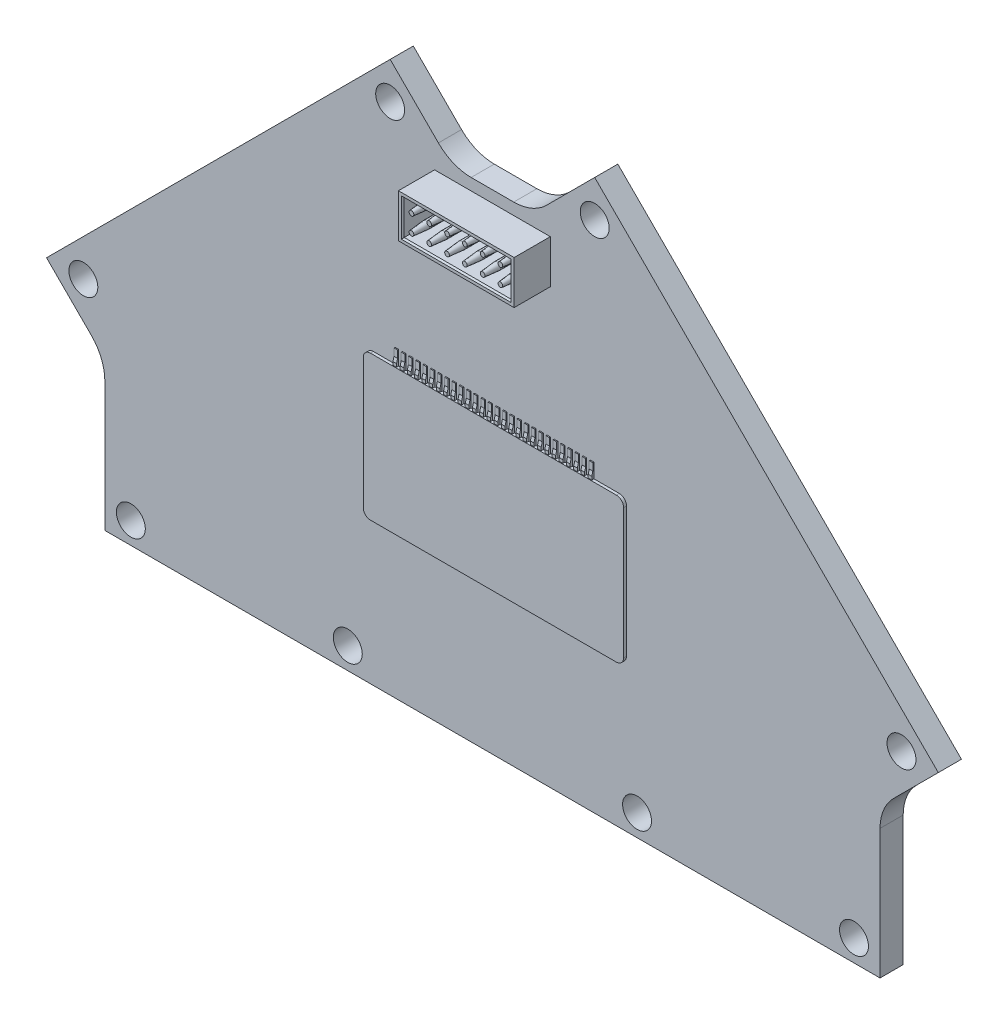
SolidWorks part; units mm, degrees
material "处理板，简单型"
ref_plane "前视基准面" through (0, 0, 0) normal (0, 0, 1) x (1, 0, 0)
ref_plane "上视基准面" through (0, 0, 0) normal (0, 1, 0) x (1, 0, 0)
ref_plane "右视基准面" through (0, 0, 0) normal (1, 0, 0) x (0, 0, -1)
sketch "Model" plane through (0, 0, 0) normal (0, 0, 1) x (1, 0, 0)
  line L7 (13.9194, -7.0717) -> (-2.0806, -7.0717)
  line L8 (-2.0806, -7.0717) -> (-2.0806, -11.9717)
  line L9 (13.9194, -7.0717) -> (13.9194, -11.9717)
  line L10 (-16.0806, -8.9717) -> (27.9194, -8.9717)
  line L11 (-19.0806, 2.9694) -> (-19.0806, -5.9717)
  line L12 (-3.143, 20.1496) -> (-18.2019, 5.0907)
  line L13 (30.9194, 2.9694) -> (30.9194, -5.9717)
  line L14 (14.9819, 20.1496) -> (30.0408, 5.0907)
  line L15 (-1.0217, 21.0283) -> (12.8606, 21.0283)
  line L17 (5.9194, -11.9717) -> (32.7194, -11.9717)
  line L18 (-20.8806, -11.9717) -> (5.9194, -11.9717)
  line L20 (32.7194, -3.0133) -> (32.7194, -11.9717)
  line L21 (36.7493, 2.342) -> (33.6567, -0.7506)
  line L22 (12.9905, 26.1008) -> (36.7493, 2.342)
  line L23 (12.9905, 26.1008) -> (9.6553, 22.7656)
  line L24 (4.4463, 21.8283) -> (7.3925, 21.8283)
  line L25 (-1.1516, 26.1008) -> (2.1836, 22.7656)
  line L26 (-1.1516, 26.1008) -> (-24.9104, 2.342)
  line L27 (-24.9104, 2.342) -> (-21.8178, -0.7506)
  line L28 (-20.8806, -3.0133) -> (-20.8806, -11.9717)
  arc A4 (-19.0806, -5.9717) -> (-16.0806, -8.9717) centre (-16.0806, -5.9717) ccw
  arc A5 (-18.2019, 5.0907) -> (-19.0806, 2.9694) centre (-16.0806, 2.9694) ccw
  arc A6 (27.9194, -8.9717) -> (30.9194, -5.9717) centre (27.9194, -5.9717) ccw
  arc A7 (30.9194, 2.9694) -> (30.0408, 5.0907) centre (27.9194, 2.9694) ccw
  arc A8 (14.9819, 20.1496) -> (12.8606, 21.0283) centre (12.8606, 18.0283) ccw
  arc A9 (-1.0217, 21.0283) -> (-3.143, 20.1496) centre (-1.0217, 18.0283) ccw
  circle A10 centre (12.9905, 23.5552) radius 1
  circle A11 centre (-1.1516, 23.5552) radius 1
  circle A12 centre (-22.3648, 2.342) radius 1
  circle A13 centre (-19.0806, -10.4717) radius 1
  circle A14 centre (-4.0806, -10.4717) radius 1
  circle A15 centre (15.9194, -10.4717) radius 1
  circle A16 centre (30.9194, -10.4717) radius 1
  circle A17 centre (34.2037, 2.342) radius 1
  arc A18 (33.6567, -0.7506) -> (32.7194, -3.0133) centre (35.9194, -3.0133) ccw
  arc A19 (7.3925, 21.8283) -> (9.6553, 22.7656) centre (7.3925, 25.0283) ccw
  arc A20 (2.1836, 22.7656) -> (4.4463, 21.8283) centre (4.4463, 25.0283) ccw
  arc A21 (-20.8806, -3.0133) -> (-21.8178, -0.7506) centre (-24.0806, -3.0133) ccw
extrude "凸台-拉伸1" add sketch "Model" along normal blind 1.6 contours A21 L28 L18 L8 L10 A4 L11 A5 L12 A9 L15 A8 L14 A7 L13 A6 L9 L17 L20 A18 L21 L22 L23 A19 L24 A20 L25 L26 L27 A17 A16 A15 A14 A13 A12 A11 A10 | L8 L18 L17 L9 L10 | L15 A9 L12 A5 L11 A4 L10 L8 L7 L9 A6 L13 A7 L14 A8 | L8 L10 L9 L7 region at (5.9194, -8.0217, 0) region at (5.9194, 4.1849, 0) region at (20.9194, -9.6964, 0) region at (5.9194, -10.4717, 0)
sketch "草图1" plane through (0, 0, 1.6) normal (0, 0, 1) x (1, 0, 0)
  line L0 (-20.8806, -11.9717) -> (32.7194, -11.9717) construction
  line L1 (-2.3112, 8.0283) -> (14.6888, 8.0283)
  line L2 (-2.8112, 7.5283) -> (-2.8112, -1.4717)
  line L3 (-2.3112, -1.9717) -> (14.6888, -1.9717)
  line L4 (15.1888, 7.5283) -> (15.1888, -1.4717)
  line L5 (-2.8112, 8.0283) -> (15.1888, -1.9717) construction
  line L6 (-2.8112, -1.9717) -> (15.1888, 8.0283) construction
  arc A0 (14.6888, 8.0283) -> (15.1888, 7.5283) centre (14.6888, 7.5283) cw
  arc A1 (15.1888, -1.4717) -> (14.6888, -1.9717) centre (14.6888, -1.4717) cw
  arc A2 (-2.3112, -1.9717) -> (-2.8112, -1.4717) centre (-2.3112, -1.4717) cw
  arc A3 (-2.8112, 7.5283) -> (-2.3112, 8.0283) centre (-2.3112, 7.5283) cw
  point P0 (6.1888, 3.0283)
  dimension "D4" = 0.5
  dimension "D1" = 18
  dimension "D2" = 10
  dimension "D3" = 10
extrude "凸台-拉伸2" add sketch "草图1" along normal blind 0.2
sketch "草图2" plane through (0, 0, 1.6) normal (0, 0, 1) x (1, 0, 0)
  line L1 (1.9194, 21.0201) -> (9.9194, 21.0201)
  line L2 (1.9194, 21.0201) -> (1.9194, 18.0201)
  line L3 (1.9194, 18.0201) -> (9.9194, 18.0201)
  line L4 (9.9194, 21.0201) -> (9.9194, 18.0201)
  line L7 (4.4463, 21.8283) -> (7.3925, 21.8283) construction
  line L8 (2.2194, 20.7201) -> (9.6194, 20.7201)
  line L9 (9.6194, 20.7201) -> (9.6194, 18.3201)
  line L10 (2.2194, 18.3201) -> (9.6194, 18.3201)
  line L11 (2.2194, 20.7201) -> (2.2194, 18.3201)
  circle A0 centre (2.8194, 20.1201) radius 0.25
  circle A1 centre (2.8194, 18.9201) radius 0.25
  circle A2 centre (4.0494, 20.1201) radius 0.25
  circle A3 centre (4.0494, 18.9201) radius 0.25
  circle A4 centre (5.2794, 20.1201) radius 0.25
  circle A5 centre (5.2794, 18.9201) radius 0.25
  circle A6 centre (6.5094, 20.1201) radius 0.25
  circle A7 centre (6.5094, 18.9201) radius 0.25
  circle A8 centre (7.7394, 20.1201) radius 0.25
  circle A9 centre (7.7394, 18.9201) radius 0.25
  circle A10 centre (8.9694, 20.1201) radius 0.25
  circle A11 centre (8.9694, 18.9201) radius 0.25
  dimension "D3" = 0.5
  dimension "D5" = 0.5
  dimension "D6" = 0.6
  dimension "D7" = 0.6
  dimension "D8" = 0.6
  dimension "D9" = 0.6
  dimension "D1" = 8
  dimension "D2" = 3
  dimension "D4" = 0.3
  dimension "D10" = 6
extrude "凸台-拉伸3" add sketch "草图2" along normal blind 2.5 contours L4 L1 L2 L3 L11 L8 L9 L10 | A1 | A0 | A2 | A3 | A4 | A5 | A6 | A7 | A8 | A9 | A11 | A10 region at (5.9194, 20.9347, 1.6) region at (2.8194, 20.1201, 1.6) region at (2.8194, 18.9201, 1.6) region at (4.0494, 20.1201, 1.6) region at (4.0494, 18.9201, 1.6) region at (5.2794, 20.1201, 1.6) region at (5.2794, 18.9201, 1.6) region at (6.5094, 20.1201, 1.6) region at (6.5094, 18.9201, 1.6) region at (7.7394, 20.1201, 1.6) region at (7.7394, 18.9201, 1.6) region at (8.9694, 20.1201, 1.6) region at (8.9694, 18.9201, 1.6)
chamfer "倒角1" distance 1 angle 5 1 edges at (9.2194, 18.9201, 4.1) first distance on face at (9.2194, 18.9201, 4.1)
chamfer "倒角2" distance 1 angle 5 11 edges at (4.2994, 20.1201, 4.1) (3.0694, 20.1201, 4.1) (3.0694, 18.9201, 4.1) (4.2994, 18.9201, 4.1) (5.5294, 20.1201, 4.1) (5.5294, 18.9201, 4.1) (6.7594, 20.1201, 4.1) (6.7594, 18.9201, 4.1) (7.9894, 20.1201, 4.1) (7.9894, 18.9201, 4.1) (9.2194, 20.1201, 4.1) first distance on face at (4.2994, 20.1201, 4.1) first distance on face at (3.0694, 20.1201, 4.1) first distance on face at (3.0694, 18.9201, 4.1) first distance on face at (4.2994, 18.9201, 4.1) first distance on face at (5.5294, 20.1201, 4.1) first distance on face at (5.5294, 18.9201, 4.1) first distance on face at (6.7594, 20.1201, 4.1) first distance on face at (6.7594, 18.9201, 4.1) first distance on face at (7.9894, 20.1201, 4.1) first distance on face at (7.9894, 18.9201, 4.1) first distance on face at (9.2194, 20.1201, 4.1)
chamfer "倒角3" distance 0.1 angle 45 4 edges at (9.6194, 19.5201, 4.1) (5.9194, 20.7201, 4.1) (2.2194, 19.5201, 4.1) (5.9194, 18.3201, 4.1)
sketch "草图4" plane through (0, 0, 0) normal (0, 0, -1) x (-1, 0, 0)
  line L0 (20.8806, -11.9717) -> (-32.7194, -11.9717) construction
  line L1 (-10.9194, -11.9717) -> (-0.9194, -11.9717)
  line L2 (-10.9194, -11.9717) -> (-10.9194, -8.9717)
  line L3 (-10.9194, -8.9717) -> (-0.9194, -8.9717)
  line L4 (-0.9194, -11.9717) -> (-0.9194, -8.9717)
  circle A0 centre (-15.9194, -10.4717) radius 1 construction
  dimension "D3" = 5
  dimension "D1" = 10
  dimension "D2" = 3
extrude "凸台-拉伸5" add sketch "草图4" along normal blind 2
sketch "草图6" plane through (0, 0, -2) normal (0, 0, -1) x (-1, 0, 0)
  line L0 (-10.9194, -11.9717) -> (-0.9194, -11.9717) construction
  line L1 (-9.9194, -11.4717) -> (-1.9194, -11.4717)
  line L2 (-9.9194, -11.4717) -> (-9.9194, -11.9717)
  line L3 (-9.9194, -11.9717) -> (-1.9194, -11.9717)
  line L4 (-1.9194, -11.4717) -> (-1.9194, -11.9717)
  line L5 (-0.9194, -11.9717) -> (-0.9194, -8.9717) construction
  dimension "D1" = 8
  dimension "D2" = 1
  dimension "D3" = 0.5
extrude "切除-拉伸1" cut sketch "草图6" against normal blind 1
sketch "草图7" plane through (0, -11.9717, 0) normal (0, -1, 0) x (1, 0, 0)
  line L0 (-20.8806, 0) -> (0.9194, 0) construction
  line L1 (1.2194, 0) -> (10.6194, 0)
  line L2 (1.2194, 0) -> (1.2194, -1.7)
  line L3 (1.2194, -1.7) -> (10.6194, -1.7)
  line L4 (10.6194, 0) -> (10.6194, -1.7)
  line L5 (0.9194, -2) -> (0.9194, 0) construction
  line L6 (10.9194, -2) -> (10.9194, 0) construction
  point P6 (0.9194, -1)
  dimension "D1" = 1.7
  dimension "D2" = 0
  dimension "D3" = 0.3
  dimension "D4" = 0.3
extrude "切除-拉伸2" cut sketch "草图7" against normal blind 2.7
sketch "草图11" plane through (0, -9.2717, 0) normal (0, -1, 0) x (1, 0, 0)
  line L0 (1.2194, 0) -> (1.2194, -1.7) construction
  circle A0 centre (2.1694, -0.85) radius 0.25
  circle A1 centre (3.6694, -0.85) radius 0.25
  circle A2 centre (5.1694, -0.85) radius 0.25
  circle A3 centre (6.6694, -0.85) radius 0.25
  circle A4 centre (8.1694, -0.85) radius 0.25
  circle A5 centre (9.6694, -0.85) radius 0.25
  point P2 (1.2194, -0.85)
  dimension "D1" = 0.5
  dimension "D2" = 0.95
  dimension "D3" = 6
extrude "凸台-拉伸9" add sketch "草图11" along normal blind 2.5
chamfer "倒角6" distance 1 angle 5 6 edges at (6.6694, -11.7717, -1.1) (3.6694, -11.7717, -1.1) (9.6694, -11.7717, -1.1) (8.1694, -11.7717, -1.1) (5.1694, -11.7717, -1.1) (2.1694, -11.7717, -1.1) first distance on face at (6.6694, -11.7717, -1.1) first distance on face at (3.6694, -11.7717, -1.1) first distance on face at (9.6694, -11.7717, -1.1) first distance on face at (8.1694, -11.7717, -1.1) first distance on face at (5.1694, -11.7717, -1.1) first distance on face at (2.1694, -11.7717, -1.1)
sketch "草图12" plane through (0, 0, 0) normal (0, 0, -1) x (-1, 0, 0)
  line L0 (-0.9194, -8.9717) -> (-10.9194, -8.9717) construction
  line L1 (-9.9694, -7.9717) -> (-9.6694, -7.9717)
  line L2 (-9.9694, -7.9717) -> (-9.9694, -8.9717)
  line L3 (-9.9694, -8.9717) -> (-9.6694, -8.9717)
  line L4 (-9.6694, -7.9717) -> (-9.6694, -8.9717)
  line L5 (-10.9194, -8.9717) -> (-10.9194, -11.9717) construction
  line L6 (-8.4694, -7.9717) -> (-8.1694, -7.9717)
  line L7 (-8.4694, -7.9717) -> (-8.4694, -8.9717)
  line L8 (-8.1694, -7.9717) -> (-8.1694, -8.9717)
  line L9 (-8.4694, -8.9717) -> (-8.1694, -8.9717)
  line L10 (-6.9694, -7.9717) -> (-6.6694, -7.9717)
  line L11 (-6.9694, -7.9717) -> (-6.9694, -8.9717)
  line L12 (-6.6694, -7.9717) -> (-6.6694, -8.9717)
  line L13 (-6.9694, -8.9717) -> (-6.6694, -8.9717)
  line L14 (-5.4694, -7.9717) -> (-5.1694, -7.9717)
  line L15 (-5.4694, -7.9717) -> (-5.4694, -8.9717)
  line L16 (-5.1694, -7.9717) -> (-5.1694, -8.9717)
  line L17 (-5.4694, -8.9717) -> (-5.1694, -8.9717)
  line L18 (-3.9694, -7.9717) -> (-3.6694, -7.9717)
  line L19 (-3.9694, -7.9717) -> (-3.9694, -8.9717)
  line L20 (-3.6694, -7.9717) -> (-3.6694, -8.9717)
  line L21 (-3.9694, -8.9717) -> (-3.6694, -8.9717)
  line L22 (-2.4694, -7.9717) -> (-2.1694, -7.9717)
  line L23 (-2.4694, -7.9717) -> (-2.4694, -8.9717)
  line L24 (-2.1694, -7.9717) -> (-2.1694, -8.9717)
  line L25 (-2.4694, -8.9717) -> (-2.1694, -8.9717)
  dimension "D1" = 0.3
  dimension "D2" = 1
  dimension "D3" = 0.95
  dimension "D4" = 6
extrude "凸台-拉伸10" add sketch "草图12" along normal blind 1.5
sketch "草图13" plane through (9.9694, 0, 0) normal (1, 0, 0) x (0, 0, -1)
  line L0 (0.75, -7.9717) -> (1.5, -8.4717)
  line L1 (1.5, -7.9717) -> (0, -7.9717) construction
  line L2 (1.5, -7.9717) -> (1.5, -8.9717) construction
  line L3 (1.5, -8.4717) -> (1.5, -7.9717)
  line L4 (1.5, -7.9717) -> (0.75, -7.9717)
extrude "切除-拉伸4" cut sketch "草图13" against normal blind 8.5
sketch "草图14" plane through (9.9694, 0, 0) normal (1, 0, 0) x (0, 0, -1)
  line L0 (0, -8.6717) -> (0, -8.9717)
  line L1 (0, -7.9717) -> (0, -8.9717) construction
  line L2 (0, -8.9717) -> (0.5615, -8.9717)
  line L3 (1.5, -8.9717) -> (0, -8.9717) construction
  line L4 (0.5615, -8.9717) -> (0.2, -8.6717)
  line L5 (0.2, -8.6717) -> (0, -8.6717)
  line L6 (0.75, -7.9717) -> (1.5, -8.4717) construction
  dimension "D1" = 0.3
  dimension "D2" = 0.2
  dimension "D3" = 6
extrude "切除-拉伸5" cut sketch "草图14" against normal blind 8.5
sketch "草图15" plane through (0, 0, 0) normal (0, 0, -1) x (-1, 0, 0)
  line L0 (20.8806, -11.9717) -> (-0.9194, -11.9717) construction
  line L1 (-11.9194, 10.0283) -> (0.0806, 10.0283)
  line L2 (-11.9194, 10.0283) -> (-11.9194, -1.9717)
  line L3 (-11.9194, -1.9717) -> (0.0806, -1.9717)
  line L4 (0.0806, 10.0283) -> (0.0806, -1.9717)
  line L5 (-11.9194, 10.0283) -> (0.0806, -1.9717) construction
  line L6 (-11.9194, -1.9717) -> (0.0806, 10.0283) construction
  point P0 (-5.9194, 4.0283)
  dimension "D1" = 16
  dimension "D2" = 12
  dimension "D3" = 12
extrude "凸台-拉伸11" add sketch "草图15" along normal blind 1.2
chamfer "倒角7" distance 0.2 angle 45 4 edges at (5.9194, -1.9717, -1.2) (-0.0806, 4.0283, -1.2) (11.9194, 4.0283, -1.2) (5.9194, 10.0283, -1.2)
chamfer "倒角8" distance 0.2 angle 45 4 edges at (11.9194, -1.9717, -0.5) (-0.0806, -1.9717, -0.5) (-0.0806, 10.0283, -0.5) (11.9194, 10.0283, -0.5)
sketch "草图16" plane through (0, 0, 0) normal (0, 0, -1) x (-1, 0, 0)
  line L0 (-11.9194, 9.8283) -> (-11.9194, -1.7717) construction
  line L1 (-21.9194, 11.0283) -> (-16.9194, 11.0283)
  line L2 (-21.9194, 11.0283) -> (-21.9194, 6.0283)
  line L3 (-21.9194, 6.0283) -> (-16.9194, 6.0283)
  line L4 (-16.9194, 11.0283) -> (-16.9194, 6.0283)
  line L5 (-21.9194, 11.0283) -> (-16.9194, 6.0283) construction
  line L6 (-21.9194, 6.0283) -> (-16.9194, 11.0283) construction
  line L7 (-10.9194, -11.9717) -> (-32.7194, -11.9717) construction
  point P0 (-19.4194, 8.5283)
  dimension "D1" = 5
  dimension "D2" = 5
  dimension "D3" = 5
  dimension "D4" = 18
extrude "凸台-拉伸12" add sketch "草图16" along normal blind 1.2
sketch "草图17" plane through (0, 0, 0) normal (0, 0, -1) x (-1, 0, 0)
  line L0 (0.0806, -1.7717) -> (0.0806, 9.8283) construction
  line L1 (4.0806, 5.5424) -> (7.0806, 5.5424)
  line L2 (4.0806, 5.5424) -> (4.0806, 0.5424)
  line L3 (4.0806, 0.5424) -> (7.0806, 0.5424)
  line L4 (7.0806, 5.5424) -> (7.0806, 0.5424)
  line L5 (11.0806, 3.0283) -> (16.0806, 3.0283)
  line L6 (11.0806, 3.0283) -> (11.0806, 0.0283)
  line L7 (11.0806, 0.0283) -> (16.0806, 0.0283)
  line L8 (16.0806, 3.0283) -> (16.0806, 0.0283)
  line L9 (20.8806, -11.9717) -> (-0.9194, -11.9717) construction
  line L11 (-21.5783, 0.2667) -> (-19.5783, 0.2667)
  line L12 (-21.5783, 0.2667) -> (-21.5783, -2.7333)
  line L13 (-21.5783, -2.7333) -> (-19.5783, -2.7333)
  line L14 (-19.5783, 0.2667) -> (-19.5783, -2.7333)
  dimension "D1" = 3
  dimension "D2" = 5
  dimension "D3" = 4
  dimension "D4" = 5
  dimension "D5" = 3
  dimension "D6" = 12
  dimension "D7" = 4
  dimension "D8" = 3
  dimension "D9" = 2
extrude "凸台-拉伸13" add sketch "草图17" along normal blind 1.2
chamfer "倒角9" distance 0.2 angle 45 16 edges at (-13.5806, 3.0283, -1.2) (-16.0806, 1.5283, -1.2) (-13.5806, 0.0283, -1.2) (-11.0806, 1.5283, -1.2) (-5.5806, 5.5424, -1.2) (-7.0806, 3.0424, -1.2) (-5.5806, 0.5424, -1.2) (-4.0806, 3.0424, -1.2) (20.5783, 0.2667, -1.2) (19.5783, -1.2333, -1.2) (20.5783, -2.7333, -1.2) (21.5783, -1.2333, -1.2) (19.4194, 6.0283, -1.2) (21.9194, 8.5283, -1.2) (19.4194, 11.0283, -1.2) (16.9194, 8.5283, -1.2)
chamfer "倒角10" distance 0.2 angle 45 16 edges at (-16.0806, 0.0283, -0.5) (-16.0806, 3.0283, -0.5) (-11.0806, 3.0283, -0.5) (-11.0806, 0.0283, -0.5) (-7.0806, 0.5424, -0.5) (-7.0806, 5.5424, -0.5) (-4.0806, 5.5424, -0.5) (-4.0806, 0.5424, -0.5) (19.5783, 0.2667, -0.5) (21.5783, 0.2667, -0.5) (19.5783, -2.7333, -0.5) (21.5783, -2.7333, -0.5) (21.9194, 6.0283, -0.5) (16.9194, 6.0283, -0.5) (16.9194, 11.0283, -0.5) (21.9194, 11.0283, -0.5)
sketch "草图18" plane through (0, 0, 0) normal (0, 0, -1) x (-1, 0, 0)
  line L0 (-16.9194, 6.2283) -> (-16.9194, 10.8283) construction
  line L1 (-16.9194, 10.5283) -> (-15.7194, 10.5283)
  line L2 (-16.9194, 10.5283) -> (-16.9194, 10.2283)
  line L3 (-16.9194, 10.2283) -> (-15.7194, 10.2283)
  line L4 (-15.7194, 10.5283) -> (-15.7194, 10.2283)
  line L5 (-21.7194, 11.0283) -> (-17.1194, 11.0283) construction
  line L6 (-16.9194, 9.9283) -> (-15.7194, 9.9283)
  line L7 (-16.9194, 9.6283) -> (-15.7194, 9.6283)
  line L8 (-15.7194, 9.9283) -> (-15.7194, 9.6283)
  line L9 (-16.9194, 9.9283) -> (-16.9194, 9.6283)
  line L10 (-16.9194, 9.3283) -> (-15.7194, 9.3283)
  line L11 (-16.9194, 9.0283) -> (-15.7194, 9.0283)
  line L12 (-15.7194, 9.3283) -> (-15.7194, 9.0283)
  line L13 (-16.9194, 9.3283) -> (-16.9194, 9.0283)
  line L14 (-16.9194, 8.7283) -> (-15.7194, 8.7283)
  line L15 (-16.9194, 8.4283) -> (-15.7194, 8.4283)
  line L16 (-15.7194, 8.7283) -> (-15.7194, 8.4283)
  line L17 (-16.9194, 8.7283) -> (-16.9194, 8.4283)
  line L18 (-16.9194, 8.1283) -> (-15.7194, 8.1283)
  line L19 (-16.9194, 7.8283) -> (-15.7194, 7.8283)
  line L20 (-15.7194, 8.1283) -> (-15.7194, 7.8283)
  line L21 (-16.9194, 8.1283) -> (-16.9194, 7.8283)
  line L22 (-16.9194, 7.5283) -> (-15.7194, 7.5283)
  line L23 (-16.9194, 7.2283) -> (-15.7194, 7.2283)
  line L24 (-15.7194, 7.5283) -> (-15.7194, 7.2283)
  line L25 (-16.9194, 7.5283) -> (-16.9194, 7.2283)
  line L26 (-16.9194, 6.9283) -> (-15.7194, 6.9283)
  line L27 (-16.9194, 6.6283) -> (-15.7194, 6.6283)
  line L28 (-15.7194, 6.9283) -> (-15.7194, 6.6283)
  line L29 (-16.9194, 6.9283) -> (-16.9194, 6.6283)
  line L31 (-21.9194, 10.8283) -> (-21.9194, 6.2283) construction
  line L32 (-21.4194, 12.2283) -> (-21.1194, 12.2283)
  line L33 (-21.4194, 12.2283) -> (-21.4194, 11.0283)
  line L34 (-21.4194, 11.0283) -> (-21.1194, 11.0283)
  line L35 (-21.1194, 12.2283) -> (-21.1194, 11.0283)
  line L36 (-20.5194, 12.2283) -> (-20.5194, 11.0283)
  line L37 (-20.8194, 12.2283) -> (-20.8194, 11.0283)
  line L38 (-20.8194, 12.2283) -> (-20.5194, 12.2283)
  line L39 (-20.8194, 11.0283) -> (-20.5194, 11.0283)
  line L40 (-19.9194, 12.2283) -> (-19.9194, 11.0283)
  line L41 (-20.2194, 12.2283) -> (-20.2194, 11.0283)
  line L42 (-20.2194, 12.2283) -> (-19.9194, 12.2283)
  line L43 (-20.2194, 11.0283) -> (-19.9194, 11.0283)
  line L44 (-19.3194, 12.2283) -> (-19.3194, 11.0283)
  line L45 (-19.6194, 12.2283) -> (-19.6194, 11.0283)
  line L46 (-19.6194, 12.2283) -> (-19.3194, 12.2283)
  line L47 (-19.6194, 11.0283) -> (-19.3194, 11.0283)
  line L48 (-18.7194, 12.2283) -> (-18.7194, 11.0283)
  line L49 (-19.0194, 12.2283) -> (-19.0194, 11.0283)
  line L50 (-19.0194, 12.2283) -> (-18.7194, 12.2283)
  line L51 (-19.0194, 11.0283) -> (-18.7194, 11.0283)
  line L52 (-18.1194, 12.2283) -> (-18.1194, 11.0283)
  line L53 (-18.4194, 12.2283) -> (-18.4194, 11.0283)
  line L54 (-18.4194, 12.2283) -> (-18.1194, 12.2283)
  line L55 (-18.4194, 11.0283) -> (-18.1194, 11.0283)
  line L56 (-17.5194, 12.2283) -> (-17.5194, 11.0283)
  line L57 (-17.8194, 12.2283) -> (-17.8194, 11.0283)
  line L58 (-17.8194, 12.2283) -> (-17.5194, 12.2283)
  line L59 (-17.8194, 11.0283) -> (-17.5194, 11.0283)
  line L60 (-17.1194, 6.0283) -> (-21.7194, 6.0283) construction
  line L61 (-23.1194, 6.8283) -> (-21.9194, 6.8283)
  line L62 (-23.1194, 6.8283) -> (-23.1194, 6.5283)
  line L63 (-23.1194, 6.5283) -> (-21.9194, 6.5283)
  line L64 (-21.9194, 6.8283) -> (-21.9194, 6.5283)
  line L65 (-23.1194, 7.4283) -> (-21.9194, 7.4283)
  line L66 (-23.1194, 7.4283) -> (-23.1194, 7.1283)
  line L67 (-23.1194, 7.1283) -> (-21.9194, 7.1283)
  line L68 (-21.9194, 7.4283) -> (-21.9194, 7.1283)
  line L69 (-23.1194, 8.0283) -> (-21.9194, 8.0283)
  line L70 (-23.1194, 8.0283) -> (-23.1194, 7.7283)
  line L71 (-23.1194, 7.7283) -> (-21.9194, 7.7283)
  line L72 (-21.9194, 8.0283) -> (-21.9194, 7.7283)
  line L73 (-23.1194, 8.6283) -> (-21.9194, 8.6283)
  line L74 (-23.1194, 8.6283) -> (-23.1194, 8.3283)
  line L75 (-23.1194, 8.3283) -> (-21.9194, 8.3283)
  line L76 (-21.9194, 8.6283) -> (-21.9194, 8.3283)
  line L77 (-23.1194, 9.2283) -> (-21.9194, 9.2283)
  line L78 (-23.1194, 9.2283) -> (-23.1194, 8.9283)
  line L79 (-23.1194, 8.9283) -> (-21.9194, 8.9283)
  line L80 (-21.9194, 9.2283) -> (-21.9194, 8.9283)
  line L81 (-23.1194, 9.8283) -> (-21.9194, 9.8283)
  line L82 (-23.1194, 9.8283) -> (-23.1194, 9.5283)
  line L83 (-23.1194, 9.5283) -> (-21.9194, 9.5283)
  line L84 (-21.9194, 9.8283) -> (-21.9194, 9.5283)
  line L85 (-23.1194, 10.4283) -> (-21.9194, 10.4283)
  line L86 (-23.1194, 10.4283) -> (-23.1194, 10.1283)
  line L87 (-23.1194, 10.1283) -> (-21.9194, 10.1283)
  line L88 (-21.9194, 10.4283) -> (-21.9194, 10.1283)
  dimension "D1" = 1.2
  dimension "D2" = 0.3
  dimension "D3" = 0.5
  dimension "D5" = 1.2
  dimension "D6" = 0.3
  dimension "D7" = 0.5
  dimension "D9" = 1.2
  dimension "D10" = 0.3
  dimension "D11" = 0.5
  dimension "D4" = 7
  dimension "D8" = 7
  dimension "D12" = 7
extrude "凸台-拉伸14" add sketch "草图18" along normal blind 0.6
sketch "草图19" plane through (0, 6.6283, 0) normal (0, -1, 0) x (1, 0, 0)
  line L0 (15.7194, -0.2) -> (16.0992, -0.2)
  line L1 (15.7194, -0.6) -> (15.7194, 0) construction
  line L2 (16.0992, -0.2) -> (16.5759, -0.6)
  line L3 (16.9194, -0.6) -> (15.7194, -0.6) construction
  line L4 (16.5759, -0.6) -> (15.7194, -0.6)
  line L5 (15.7194, -0.6) -> (15.7194, -0.2)
  line L6 (16.9194, 0) -> (15.7194, 0) construction
  line L7 (16.473, 0) -> (16.9194, -0.3908)
  line L8 (10.9194, 0) -> (32.7194, 0) construction
  line L9 (16.9194, -0.6) -> (16.9194, 0) construction
  line L10 (16.9194, -0.3908) -> (16.9194, 0)
  line L11 (16.9194, 0) -> (16.473, 0)
  dimension "D1" = 0.2
  dimension "D2" = 40
  dimension "D3" = 1.2
extrude "切除-拉伸6" cut sketch "草图19" against normal blind 4.6
sketch "草图20" plane through (21.4194, 0, 0) normal (1, 0, 0) x (0, 0, -1)
  line L0 (0.2, 12.2283) -> (0.2, 11.8486)
  line L1 (0.6, 12.2283) -> (0, 12.2283) construction
  line L2 (0.2, 11.8486) -> (0.6, 11.3719)
  line L3 (0.6, 12.2283) -> (0.6, 11.0283) construction
  line L4 (0.6, 11.3719) -> (0.6, 12.2283)
  line L5 (0.6, 12.2283) -> (0.2, 12.2283)
  line L6 (0, 12.2283) -> (0, 11.0283) construction
  line L7 (0, 11.0283) -> (0, 11.4122)
  line L8 (0, 11.4122) -> (0.3361, 11.0283)
  line L9 (0.6, 11.0283) -> (0, 11.0283) construction
  line L10 (0.3361, 11.0283) -> (0, 11.0283)
  dimension "D1" = 0.2
  dimension "D2" = 40
  dimension "D3" = 1.2
extrude "切除-拉伸7" cut sketch "草图20" against normal blind 4.6
sketch "草图21" plane through (0, 10.4283, 0) normal (0, 1, 0) x (1, 0, 0)
  line L0 (23.1194, 0.2) -> (22.6256, 0.2)
  line L2 (23.1194, 0.6) -> (23.1194, 0) construction
  line L3 (22.6256, 0.2) -> (22.1489, 0.6)
  line L4 (21.9194, 0.6) -> (23.1194, 0.6) construction
  line L5 (22.1489, 0.6) -> (23.1194, 0.6)
  line L6 (23.1194, 0.6) -> (23.1194, 0.2)
  line L7 (21.9194, 0) -> (22.3441, 0)
  line L8 (12.9905, 0) -> (36.7493, 0) construction
  line L9 (22.3441, 0) -> (21.9194, 0.3717)
  line L10 (21.9194, 0.6) -> (21.9194, 0) construction
  line L11 (21.9194, 0.3717) -> (21.9194, 0)
  line L12 (21.9194, 0) -> (23.1194, 0) construction
  dimension "D1" = 0.2
  dimension "D2" = 40
  dimension "D3" = 1.2
extrude "切除-拉伸8" cut sketch "草图21" against normal blind 4.6
sketch "草图22" plane through (0, 0, 0) normal (0, 0, -1) x (-1, 0, 0)
  line L0 (-21.5783, 0.0667) -> (-21.5783, -2.5333) construction
  line L1 (-22.7783, -0.3333) -> (-21.5783, -0.3333)
  line L2 (-22.7783, -0.3333) -> (-22.7783, -0.6333)
  line L3 (-22.7783, -0.6333) -> (-21.5783, -0.6333)
  line L4 (-21.5783, -0.3333) -> (-21.5783, -0.6333)
  line L5 (-19.5783, -2.5333) -> (-19.5783, 0.0667) construction
  line L6 (-22.7783, -1.8333) -> (-21.5783, -1.8333)
  line L7 (-22.7783, -1.8333) -> (-22.7783, -2.1333)
  line L8 (-22.7783, -2.1333) -> (-21.5783, -2.1333)
  line L9 (-21.5783, -1.8333) -> (-21.5783, -2.1333)
  line L10 (-19.5783, -0.1333) -> (-18.3783, -0.1333)
  line L11 (-19.5783, -0.1333) -> (-19.5783, -0.4333)
  line L12 (-19.5783, -0.4333) -> (-18.3783, -0.4333)
  line L13 (-18.3783, -0.1333) -> (-18.3783, -0.4333)
  line L14 (-21.3783, 0.2667) -> (-19.7783, 0.2667) construction
  line L15 (-19.5783, -1.2333) -> (-18.3783, -1.2333)
  line L16 (-19.5783, -1.2333) -> (-19.5783, -1.5333)
  line L17 (-19.5783, -1.5333) -> (-18.3783, -1.5333)
  line L18 (-18.3783, -1.2333) -> (-18.3783, -1.5333)
  line L19 (-19.5783, -2.0333) -> (-18.3783, -2.0333)
  line L20 (-19.5783, -2.0333) -> (-19.5783, -2.3333)
  line L21 (-19.5783, -2.3333) -> (-18.3783, -2.3333)
  line L22 (-18.3783, -2.0333) -> (-18.3783, -2.3333)
  line L23 (-19.7783, -2.7333) -> (-21.3783, -2.7333) construction
  line L24 (-19.7783, 0.2667) -> (-21.3783, 0.2667) construction
  dimension "D1" = 0.3
  dimension "D2" = 1.2
  dimension "D3" = 1.2
  dimension "D4" = 0.3
  dimension "D5" = 0.3
  dimension "D6" = 0.3
  dimension "D7" = 0.3
  dimension "D8" = 1.2
  dimension "D9" = 1.2
  dimension "D10" = 1.2
  dimension "D11" = 0.6
  dimension "D12" = 0.6
  dimension "D13" = 0.4
  dimension "D14" = 0.4
  dimension "D15" = 1.2
extrude "凸台-拉伸15" add sketch "草图22" along normal blind 0.8
sketch "草图23" plane through (0, -2.3333, 0) normal (0, -1, 0) x (1, 0, 0)
  line L0 (18.3783, -0.2) -> (18.4633, -0.2)
  line L1 (18.3783, -0.8) -> (18.3783, 0) construction
  line L2 (18.4633, -0.2) -> (19.1783, -0.8)
  line L3 (19.5783, -0.8) -> (18.3783, -0.8) construction
  line L4 (19.1783, -0.8) -> (18.3783, -0.8)
  line L5 (18.3783, -0.8) -> (18.3783, -0.2)
  line L6 (19.5783, 0) -> (19.5783, -0.5035)
  line L7 (19.5783, -0.8) -> (19.5783, 0) construction
  line L8 (19.5783, -0.5035) -> (18.9783, 0)
  line L9 (19.5783, 0) -> (18.3783, 0) construction
  line L10 (18.9783, 0) -> (19.5783, 0)
  line L11 (19.5783, 0) -> (19.5938, -0.0006)
  line L12 (10.9194, 0) -> (32.7194, 0) construction
  line L13 (22.7783, -0.2) -> (22.6934, -0.2)
  line L14 (22.7783, -0.8) -> (22.7783, 0) construction
  line L15 (22.6934, -0.2) -> (21.9783, -0.8)
  line L16 (22.7783, -0.8) -> (21.5783, -0.8) construction
  line L17 (21.9783, -0.8) -> (22.7783, -0.8)
  line L18 (22.7783, -0.8) -> (22.7783, -0.2)
  line L19 (21.5783, 0) -> (21.5783, -0.5035)
  line L20 (21.5783, 0) -> (21.5783, -1) construction
  line L21 (21.5783, -0.5035) -> (22.1783, 0)
  line L22 (22.1783, 0) -> (21.5783, 0)
  line L23 (21.5783, 0) -> (21.5597, -0.0047)
  line M1 (19.5783, 0) -> (18.3783, 0)
  line M2 (18.3783, 0) -> (18.3783, -0.8)
  line M3 (18.3783, -0.8) -> (19.5783, -0.8)
  line M4 (19.5783, -0.8) -> (19.5783, 0)
  dimension "D1" = 0.2
  dimension "D2" = 40
  dimension "D3" = 0.8
  dimension "D4" = 360
  dimension "D5" = 0.6
  dimension "D6" = 0.2
  dimension "D7" = 0.8
  dimension "D8" = 40
  dimension "D9" = 50
  dimension "D10" = 0.6
extrude "切除-拉伸9" cut sketch "草图23" against normal blind 3.8 contours L2 L0 M2 M3 | L8 M4 M1 | L21 L22 L19 | L17 L18 L13 L15 region at (18.6477, -2.3333, -0.5808) region at (19.3783, -2.3333, -0.1678) region at (22.5089, -2.3333, -0.5808) region at (21.7783, -2.3333, -0.1678)
sketch "草图24" plane through (0, 0, 0) normal (0, 0, -1) x (-1, 0, 0)
  line L0 (11.2806, 0.0283) -> (15.8806, 0.0283) construction
  line L1 (11.6806, 0.0283) -> (11.9806, 0.0283)
  line L2 (11.6806, 0.0283) -> (11.6806, -1.1717)
  line L3 (11.6806, -1.1717) -> (11.9806, -1.1717)
  line L4 (11.9806, 0.0283) -> (11.9806, -1.1717)
  line L6 (11.0806, 2.8283) -> (11.0806, 0.2283) construction
  line L7 (12.8306, 0.0283) -> (12.8306, -1.1717)
  line L8 (13.1306, 0.0283) -> (13.1306, -1.1717)
  line L9 (12.8306, 0.0283) -> (13.1306, 0.0283)
  line L10 (12.8306, -1.1717) -> (13.1306, -1.1717)
  line L11 (13.9806, 0.0283) -> (13.9806, -1.1717)
  line L12 (14.2806, 0.0283) -> (14.2806, -1.1717)
  line L13 (13.9806, 0.0283) -> (14.2806, 0.0283)
  line L14 (13.9806, -1.1717) -> (14.2806, -1.1717)
  line L15 (15.1306, 0.0283) -> (15.1306, -1.1717)
  line L16 (15.4306, 0.0283) -> (15.4306, -1.1717)
  line L17 (15.1306, 0.0283) -> (15.4306, 0.0283)
  line L18 (15.1306, -1.1717) -> (15.4306, -1.1717)
  line L19 (11.2806, 3.0283) -> (15.8806, 3.0283) construction
  line L20 (11.6806, 4.2283) -> (11.9806, 4.2283)
  line L21 (11.6806, 4.2283) -> (11.6806, 3.0283)
  line L22 (11.6806, 3.0283) -> (11.9806, 3.0283)
  line L23 (11.9806, 4.2283) -> (11.9806, 3.0283)
  line L24 (15.8806, 3.0283) -> (11.2806, 3.0283) construction
  line L25 (12.8306, 3.0283) -> (13.1306, 3.0283)
  line L26 (12.8306, 3.0283) -> (12.8306, 4.2283)
  line L27 (12.8306, 4.2283) -> (13.1306, 4.2283)
  line L28 (13.1306, 3.0283) -> (13.1306, 4.2283)
  line L29 (13.9806, 3.0283) -> (14.2806, 3.0283)
  line L30 (13.9806, 3.0283) -> (13.9806, 4.2283)
  line L31 (13.9806, 4.2283) -> (14.2806, 4.2283)
  line L32 (14.2806, 3.0283) -> (14.2806, 4.2283)
  line L34 (15.1306, 3.0283) -> (15.4306, 3.0283)
  line L35 (15.1306, 3.0283) -> (15.1306, 4.2283)
  line L36 (15.1306, 4.2283) -> (15.4306, 4.2283)
  line L37 (15.4306, 3.0283) -> (15.4306, 4.2283)
  dimension "D1" = 0.3
  dimension "D2" = 1.2
  dimension "D3" = 0.6
  dimension "D5" = 0.3
  dimension "D6" = 1.2
  dimension "D7" = 1.2
  dimension "D8" = 1.2
  dimension "D9" = 1.2
  dimension "D4" = 4
extrude "凸台-拉伸16" add sketch "草图24" along normal blind 0.8
sketch "草图25" plane through (-15.4306, 0, 0) normal (-1, 0, 0) x (0, 0, 1)
  line L0 (-0.8, -0.2566) -> (-0.2, -0.9717)
  line L1 (-0.8, -1.1717) -> (-0.8, 0.0283) construction
  line L2 (-0.2, -0.9717) -> (-0.2, -1.1717)
  line L3 (-0.8, -1.1717) -> (0, -1.1717) construction
  line L4 (-0.2, -1.1717) -> (-0.8, -1.1717)
  line L5 (-0.8, -1.1717) -> (-0.8, -0.2566)
  line L6 (0, 0.0283) -> (-0.5035, 0.0283)
  line L7 (-0.8, 0.0283) -> (0, 0.0283) construction
  line L8 (-0.5035, 0.0283) -> (0, -0.5717)
  line L9 (0, -1.1717) -> (0, 0.0283) construction
  line L10 (0, -0.5717) -> (0, 0.0283)
  line L11 (-0.8, 4.2283) -> (-0.8, 3.3132)
  line L12 (-0.8, 3.0283) -> (-0.8, 4.2283) construction
  line L13 (-0.8, 3.3132) -> (-0.2, 4.0283)
  line L14 (-0.2, 4.0283) -> (-0.2, 4.2283)
  line L15 (-0.8, 4.2283) -> (0, 4.2283) construction
  line L16 (-0.2, 4.2283) -> (-0.8, 4.2283)
  line L17 (0, 3.0283) -> (0, 3.6283)
  line L18 (0, 3.0283) -> (0, 4.2283) construction
  line L19 (0, 3.6283) -> (-0.5035, 3.0283)
  line L20 (-0.8, 3.0283) -> (0, 3.0283) construction
  line L21 (-0.5035, 3.0283) -> (0, 3.0283)
  line L22 (0, 3.0283) -> (0.0118, 3.0187)
  line M1 (0, -1.1717) -> (0, 0.0283)
  line M2 (0, 0.0283) -> (-0.8, 0.0283)
  line M3 (-0.8, 0.0283) -> (-0.8, -1.1717)
  line M4 (-0.8, -1.1717) -> (0, -1.1717)
  dimension "D1" = 0.2
  dimension "D2" = 40
  dimension "D3" = 0.2
  dimension "D4" = 0.6
  dimension "D5" = 0.6
  dimension "D6" = 40
  dimension "D7" = 40
  dimension "D8" = 0.2
  dimension "D9" = 0.2
extrude "切除-拉伸10" cut sketch "草图25" against normal blind 4.8 contours L14 L16 L11 L13 | L19 L21 L17 | L2 L0 M3 M4 | L8 M2 M1 region at (-15.4306, -0.8547, -0.5641) region at (-15.4306, -0.1717, -0.1678) region at (-15.4306, 3.9113, -0.5641) region at (-15.4306, 3.2283, -0.1678)
sketch "草图26" plane through (0, 0, 0) normal (0, 0, -1) x (-1, 0, 0)
  line L0 (-11.7194, 10.0283) -> (-0.1194, 10.0283) construction
  line L1 (-11.3194, 11.2283) -> (-11.0194, 11.2283)
  line L2 (-11.3194, 11.2283) -> (-11.3194, 10.0283)
  line L3 (-11.3194, 10.0283) -> (-11.0194, 10.0283)
  line L4 (-11.0194, 11.2283) -> (-11.0194, 10.0283)
  line L5 (-11.9194, 9.8283) -> (-11.9194, -1.7717) construction
  line L6 (-10.5194, 11.2283) -> (-10.2194, 11.2283)
  line L7 (-10.5194, 11.2283) -> (-10.5194, 10.0283)
  line L8 (-10.2194, 11.2283) -> (-10.2194, 10.0283)
  line L9 (-10.5194, 10.0283) -> (-10.2194, 10.0283)
  line L10 (-9.7194, 11.2283) -> (-9.4194, 11.2283)
  line L11 (-9.7194, 11.2283) -> (-9.7194, 10.0283)
  line L12 (-9.4194, 11.2283) -> (-9.4194, 10.0283)
  line L13 (-9.7194, 10.0283) -> (-9.4194, 10.0283)
  line L14 (-8.9194, 11.2283) -> (-8.6194, 11.2283)
  line L15 (-8.9194, 11.2283) -> (-8.9194, 10.0283)
  line L16 (-8.6194, 11.2283) -> (-8.6194, 10.0283)
  line L17 (-8.9194, 10.0283) -> (-8.6194, 10.0283)
  line L18 (-8.1194, 11.2283) -> (-7.8194, 11.2283)
  line L19 (-8.1194, 11.2283) -> (-8.1194, 10.0283)
  line L20 (-7.8194, 11.2283) -> (-7.8194, 10.0283)
  line L21 (-8.1194, 10.0283) -> (-7.8194, 10.0283)
  line L22 (-7.3194, 11.2283) -> (-7.0194, 11.2283)
  line L23 (-7.3194, 11.2283) -> (-7.3194, 10.0283)
  line L24 (-7.0194, 11.2283) -> (-7.0194, 10.0283)
  line L25 (-7.3194, 10.0283) -> (-7.0194, 10.0283)
  line L26 (-6.5194, 11.2283) -> (-6.2194, 11.2283)
  line L27 (-6.5194, 11.2283) -> (-6.5194, 10.0283)
  line L28 (-6.2194, 11.2283) -> (-6.2194, 10.0283)
  line L29 (-6.5194, 10.0283) -> (-6.2194, 10.0283)
  line L30 (-5.7194, 11.2283) -> (-5.4194, 11.2283)
  line L31 (-5.7194, 11.2283) -> (-5.7194, 10.0283)
  line L32 (-5.4194, 11.2283) -> (-5.4194, 10.0283)
  line L33 (-5.7194, 10.0283) -> (-5.4194, 10.0283)
  line L34 (-4.9194, 11.2283) -> (-4.6194, 11.2283)
  line L35 (-4.9194, 11.2283) -> (-4.9194, 10.0283)
  line L36 (-4.6194, 11.2283) -> (-4.6194, 10.0283)
  line L37 (-4.9194, 10.0283) -> (-4.6194, 10.0283)
  line L38 (-4.1194, 11.2283) -> (-3.8194, 11.2283)
  line L39 (-4.1194, 11.2283) -> (-4.1194, 10.0283)
  line L40 (-3.8194, 11.2283) -> (-3.8194, 10.0283)
  line L41 (-4.1194, 10.0283) -> (-3.8194, 10.0283)
  line L42 (-3.3194, 11.2283) -> (-3.0194, 11.2283)
  line L43 (-3.3194, 11.2283) -> (-3.3194, 10.0283)
  line L44 (-3.0194, 11.2283) -> (-3.0194, 10.0283)
  line L45 (-3.3194, 10.0283) -> (-3.0194, 10.0283)
  line L46 (-2.5194, 11.2283) -> (-2.2194, 11.2283)
  line L47 (-2.5194, 11.2283) -> (-2.5194, 10.0283)
  line L48 (-2.2194, 11.2283) -> (-2.2194, 10.0283)
  line L49 (-2.5194, 10.0283) -> (-2.2194, 10.0283)
  line L50 (-1.7194, 11.2283) -> (-1.4194, 11.2283)
  line L51 (-1.7194, 11.2283) -> (-1.7194, 10.0283)
  line L52 (-1.4194, 11.2283) -> (-1.4194, 10.0283)
  line L53 (-1.7194, 10.0283) -> (-1.4194, 10.0283)
  line L54 (-0.9194, 11.2283) -> (-0.6194, 11.2283)
  line L55 (-0.9194, 11.2283) -> (-0.9194, 10.0283)
  line L56 (-0.6194, 11.2283) -> (-0.6194, 10.0283)
  line L57 (-0.9194, 10.0283) -> (-0.6194, 10.0283)
  line L58 (0.0806, 9.8283) -> (0.0806, -1.7717) construction
  line L59 (0.0806, 9.4283) -> (1.2806, 9.4283)
  line L60 (0.0806, 9.4283) -> (0.0806, 9.1283)
  line L61 (0.0806, 9.1283) -> (1.2806, 9.1283)
  line L62 (1.2806, 9.4283) -> (1.2806, 9.1283)
  line L63 (1.2806, 8.6283) -> (1.2806, 8.3283)
  line L64 (0.0806, 8.6283) -> (1.2806, 8.6283)
  line L65 (0.0806, 8.3283) -> (1.2806, 8.3283)
  line L66 (0.0806, 8.6283) -> (0.0806, 8.3283)
  line L67 (1.2806, 7.8283) -> (1.2806, 7.5283)
  line L68 (0.0806, 7.8283) -> (1.2806, 7.8283)
  line L69 (0.0806, 7.5283) -> (1.2806, 7.5283)
  line L70 (0.0806, 7.8283) -> (0.0806, 7.5283)
  line L71 (1.2806, 7.0283) -> (1.2806, 6.7283)
  line L72 (0.0806, 7.0283) -> (1.2806, 7.0283)
  line L73 (0.0806, 6.7283) -> (1.2806, 6.7283)
  line L74 (0.0806, 7.0283) -> (0.0806, 6.7283)
  line L75 (1.2806, 6.2283) -> (1.2806, 5.9283)
  line L76 (0.0806, 6.2283) -> (1.2806, 6.2283)
  line L77 (0.0806, 5.9283) -> (1.2806, 5.9283)
  line L78 (0.0806, 6.2283) -> (0.0806, 5.9283)
  line L79 (1.2806, 5.4283) -> (1.2806, 5.1283)
  line L80 (0.0806, 5.4283) -> (1.2806, 5.4283)
  line L81 (0.0806, 5.1283) -> (1.2806, 5.1283)
  line L82 (0.0806, 5.4283) -> (0.0806, 5.1283)
  line L83 (1.2806, 4.6283) -> (1.2806, 4.3283)
  line L84 (0.0806, 4.6283) -> (1.2806, 4.6283)
  line L85 (0.0806, 4.3283) -> (1.2806, 4.3283)
  line L86 (0.0806, 4.6283) -> (0.0806, 4.3283)
  line L87 (1.2806, 3.8283) -> (1.2806, 3.5283)
  line L88 (0.0806, 3.8283) -> (1.2806, 3.8283)
  line L89 (0.0806, 3.5283) -> (1.2806, 3.5283)
  line L90 (0.0806, 3.8283) -> (0.0806, 3.5283)
  line L91 (1.2806, 3.0283) -> (1.2806, 2.7283)
  line L92 (0.0806, 3.0283) -> (1.2806, 3.0283)
  line L93 (0.0806, 2.7283) -> (1.2806, 2.7283)
  line L94 (0.0806, 3.0283) -> (0.0806, 2.7283)
  line L95 (1.2806, 2.2283) -> (1.2806, 1.9283)
  line L96 (0.0806, 2.2283) -> (1.2806, 2.2283)
  line L97 (0.0806, 1.9283) -> (1.2806, 1.9283)
  line L98 (0.0806, 2.2283) -> (0.0806, 1.9283)
  line L99 (1.2806, 1.4283) -> (1.2806, 1.1283)
  line L100 (0.0806, 1.4283) -> (1.2806, 1.4283)
  line L101 (0.0806, 1.1283) -> (1.2806, 1.1283)
  line L102 (0.0806, 1.4283) -> (0.0806, 1.1283)
  line L103 (1.2806, 0.6283) -> (1.2806, 0.3283)
  line L104 (0.0806, 0.6283) -> (1.2806, 0.6283)
  line L105 (0.0806, 0.3283) -> (1.2806, 0.3283)
  line L106 (0.0806, 0.6283) -> (0.0806, 0.3283)
  line L107 (1.2806, -0.1717) -> (1.2806, -0.4717)
  line L108 (0.0806, -0.1717) -> (1.2806, -0.1717)
  line L109 (0.0806, -0.4717) -> (1.2806, -0.4717)
  line L110 (0.0806, -0.1717) -> (0.0806, -0.4717)
  line L111 (1.2806, -0.9717) -> (1.2806, -1.2717)
  line L112 (0.0806, -0.9717) -> (1.2806, -0.9717)
  line L113 (0.0806, -1.2717) -> (1.2806, -1.2717)
  line L114 (0.0806, -0.9717) -> (0.0806, -1.2717)
  dimension "D1" = 0.3
  dimension "D2" = 1.2
  dimension "D3" = 0.6
  dimension "D5" = 0.3
  dimension "D6" = 1.2
  dimension "D7" = 0.6
  dimension "D4" = 14
  dimension "D8" = 14
extrude "凸台-拉伸17" add sketch "草图26" along normal blind 0.8
sketch "草图27" plane through (0.6194, 0, 0) normal (-1, 0, 0) x (0, 0, 1)
  line L0 (-0.8, 11.2283) -> (-0.2, 11.2283)
  line L1 (-0.8, 11.2283) -> (0, 11.2283) construction
  line L2 (-0.2, 11.2283) -> (-0.2, 11.0283)
  line L3 (-0.2, 11.0283) -> (-0.8, 10.3132)
  line L4 (-0.8, 10.0283) -> (-0.8, 11.2283) construction
  line L5 (0, 10.0283) -> (-0.5035, 10.0283)
  line L6 (-0.8, 11.2283) -> (-0.8, 10.3132)
  line L7 (-0.8, 10.0283) -> (0, 10.0283) construction
  line L8 (-0.5035, 10.0283) -> (0, 10.6283)
  line L9 (0, 26.1008) -> (0, 2.342) construction
  line L10 (0, 10.6283) -> (0, 10.0283)
  dimension "D1" = 0.6
  dimension "D2" = 50
  dimension "D3" = 40
  dimension "D4" = 0.2
  dimension "D5" = 0.2
extrude "切除-拉伸11" cut sketch "草图27" against normal blind 12.8
sketch "草图28" plane through (0, 9.4283, 0) normal (0, 1, 0) x (1, 0, 0)
  line L0 (-1.2806, 0.8) -> (-0.3655, 0.8)
  line L1 (-1.2806, 0.8) -> (-0.0806, 0.8) construction
  line L2 (-0.3655, 0.8) -> (-1.0806, 0.2)
  line L3 (-1.0806, 0.2) -> (-1.2806, 0.2)
  line L4 (-1.2806, 0.8) -> (-1.2806, 0) construction
  line L5 (-1.2806, 0.2) -> (-1.2806, 0.8)
  line L6 (-0.0806, 0.5035) -> (-0.6806, 0)
  line L7 (-0.0806, 0.8) -> (-0.0806, 0) construction
  line L8 (-1.2806, 0) -> (-0.0806, 0) construction
  line L9 (-0.6806, 0) -> (-0.0806, 0)
  line L10 (-0.0806, 0) -> (-0.0806, 0.5035)
  line L11 (-0.0806, 0.5035) -> (-0.0806, 0.5097)
  line M1 (-1.2806, 0) -> (-0.0806, 0)
  line M2 (-0.0806, 0) -> (-0.0806, 0.8)
  line M3 (-0.0806, 0.8) -> (-1.2806, 0.8)
  line M4 (-1.2806, 0.8) -> (-1.2806, 0)
  dimension "D1" = 40
  dimension "D2" = 0.6
  dimension "D3" = 40
  dimension "D4" = 0.2
  dimension "D5" = 0.2
extrude "切除-拉伸12" cut sketch "草图28" against normal blind 12.8 contours L3 L2 M3 M4 | L6 M2 M1 region at (-0.9636, 9.4283, -0.5641) region at (-0.2806, 9.4283, -0.1678)
sketch "草图29" plane through (0, 0, 0) normal (0, 0, -1) x (-1, 0, 0)
  line L0 (-11.7194, -1.9717) -> (-0.1194, -1.9717) construction
  line L1 (-11.3194, -1.9717) -> (-11.0194, -1.9717)
  line L2 (-11.3194, -1.9717) -> (-11.3194, -3.1717)
  line L3 (-11.3194, -3.1717) -> (-11.0194, -3.1717)
  line L4 (-11.0194, -1.9717) -> (-11.0194, -3.1717)
  line L5 (-11.9194, 9.8283) -> (-11.9194, -1.7717) construction
  line L6 (-10.5194, -1.9717) -> (-10.5194, -3.1717)
  line L7 (-10.5194, -1.9717) -> (-10.2194, -1.9717)
  line L8 (-10.2194, -1.9717) -> (-10.2194, -3.1717)
  line L9 (-10.5194, -3.1717) -> (-10.2194, -3.1717)
  line L10 (-9.7194, -1.9717) -> (-9.7194, -3.1717)
  line L11 (-9.7194, -1.9717) -> (-9.4194, -1.9717)
  line L12 (-9.4194, -1.9717) -> (-9.4194, -3.1717)
  line L13 (-9.7194, -3.1717) -> (-9.4194, -3.1717)
  line L14 (-8.9194, -1.9717) -> (-8.9194, -3.1717)
  line L15 (-8.9194, -1.9717) -> (-8.6194, -1.9717)
  line L16 (-8.6194, -1.9717) -> (-8.6194, -3.1717)
  line L17 (-8.9194, -3.1717) -> (-8.6194, -3.1717)
  line L18 (-8.1194, -1.9717) -> (-8.1194, -3.1717)
  line L19 (-8.1194, -1.9717) -> (-7.8194, -1.9717)
  line L20 (-7.8194, -1.9717) -> (-7.8194, -3.1717)
  line L21 (-8.1194, -3.1717) -> (-7.8194, -3.1717)
  line L22 (-7.3194, -1.9717) -> (-7.3194, -3.1717)
  line L23 (-7.3194, -1.9717) -> (-7.0194, -1.9717)
  line L24 (-7.0194, -1.9717) -> (-7.0194, -3.1717)
  line L25 (-7.3194, -3.1717) -> (-7.0194, -3.1717)
  line L26 (-6.5194, -1.9717) -> (-6.5194, -3.1717)
  line L27 (-6.5194, -1.9717) -> (-6.2194, -1.9717)
  line L28 (-6.2194, -1.9717) -> (-6.2194, -3.1717)
  line L29 (-6.5194, -3.1717) -> (-6.2194, -3.1717)
  line L30 (-5.7194, -1.9717) -> (-5.7194, -3.1717)
  line L31 (-5.7194, -1.9717) -> (-5.4194, -1.9717)
  line L32 (-5.4194, -1.9717) -> (-5.4194, -3.1717)
  line L33 (-5.7194, -3.1717) -> (-5.4194, -3.1717)
  line L34 (-4.9194, -1.9717) -> (-4.9194, -3.1717)
  line L35 (-4.9194, -1.9717) -> (-4.6194, -1.9717)
  line L36 (-4.6194, -1.9717) -> (-4.6194, -3.1717)
  line L37 (-4.9194, -3.1717) -> (-4.6194, -3.1717)
  line L38 (-4.1194, -1.9717) -> (-4.1194, -3.1717)
  line L39 (-4.1194, -1.9717) -> (-3.8194, -1.9717)
  line L40 (-3.8194, -1.9717) -> (-3.8194, -3.1717)
  line L41 (-4.1194, -3.1717) -> (-3.8194, -3.1717)
  line L42 (-3.3194, -1.9717) -> (-3.3194, -3.1717)
  line L43 (-3.3194, -1.9717) -> (-3.0194, -1.9717)
  line L44 (-3.0194, -1.9717) -> (-3.0194, -3.1717)
  line L45 (-3.3194, -3.1717) -> (-3.0194, -3.1717)
  line L46 (-2.5194, -1.9717) -> (-2.5194, -3.1717)
  line L47 (-2.5194, -1.9717) -> (-2.2194, -1.9717)
  line L48 (-2.2194, -1.9717) -> (-2.2194, -3.1717)
  line L49 (-2.5194, -3.1717) -> (-2.2194, -3.1717)
  line L50 (-1.7194, -1.9717) -> (-1.7194, -3.1717)
  line L51 (-1.7194, -1.9717) -> (-1.4194, -1.9717)
  line L52 (-1.4194, -1.9717) -> (-1.4194, -3.1717)
  line L53 (-1.7194, -3.1717) -> (-1.4194, -3.1717)
  line L54 (-0.9194, -1.9717) -> (-0.9194, -3.1717)
  line L55 (-0.9194, -1.9717) -> (-0.6194, -1.9717)
  line L56 (-0.6194, -1.9717) -> (-0.6194, -3.1717)
  line L57 (-0.9194, -3.1717) -> (-0.6194, -3.1717)
  line L58 (-0.1194, 10.0283) -> (-11.7194, 10.0283) construction
  line L59 (-13.1194, 9.4283) -> (-11.9194, 9.4283)
  line L60 (-13.1194, 9.4283) -> (-13.1194, 9.1283)
  line L61 (-13.1194, 9.1283) -> (-11.9194, 9.1283)
  line L62 (-11.9194, 9.4283) -> (-11.9194, 9.1283)
  line L63 (-13.1194, 8.6283) -> (-11.9194, 8.6283)
  line L64 (-13.1194, 8.6283) -> (-13.1194, 8.3283)
  line L65 (-13.1194, 8.3283) -> (-11.9194, 8.3283)
  line L66 (-11.9194, 8.6283) -> (-11.9194, 8.3283)
  line L67 (-13.1194, 7.8283) -> (-11.9194, 7.8283)
  line L68 (-13.1194, 7.8283) -> (-13.1194, 7.5283)
  line L69 (-13.1194, 7.5283) -> (-11.9194, 7.5283)
  line L70 (-11.9194, 7.8283) -> (-11.9194, 7.5283)
  line L71 (-13.1194, 7.0283) -> (-11.9194, 7.0283)
  line L72 (-13.1194, 7.0283) -> (-13.1194, 6.7283)
  line L73 (-13.1194, 6.7283) -> (-11.9194, 6.7283)
  line L74 (-11.9194, 7.0283) -> (-11.9194, 6.7283)
  line L75 (-13.1194, 6.2283) -> (-11.9194, 6.2283)
  line L76 (-13.1194, 6.2283) -> (-13.1194, 5.9283)
  line L77 (-13.1194, 5.9283) -> (-11.9194, 5.9283)
  line L78 (-11.9194, 6.2283) -> (-11.9194, 5.9283)
  line L79 (-13.1194, 5.4283) -> (-11.9194, 5.4283)
  line L80 (-13.1194, 5.4283) -> (-13.1194, 5.1283)
  line L81 (-13.1194, 5.1283) -> (-11.9194, 5.1283)
  line L82 (-11.9194, 5.4283) -> (-11.9194, 5.1283)
  line L83 (-13.1194, 4.6283) -> (-11.9194, 4.6283)
  line L84 (-13.1194, 4.6283) -> (-13.1194, 4.3283)
  line L85 (-13.1194, 4.3283) -> (-11.9194, 4.3283)
  line L86 (-11.9194, 4.6283) -> (-11.9194, 4.3283)
  line L87 (-13.1194, 3.8283) -> (-11.9194, 3.8283)
  line L88 (-13.1194, 3.8283) -> (-13.1194, 3.5283)
  line L89 (-13.1194, 3.5283) -> (-11.9194, 3.5283)
  line L90 (-11.9194, 3.8283) -> (-11.9194, 3.5283)
  line L91 (-13.1194, 3.0283) -> (-11.9194, 3.0283)
  line L92 (-13.1194, 3.0283) -> (-13.1194, 2.7283)
  line L93 (-13.1194, 2.7283) -> (-11.9194, 2.7283)
  line L94 (-11.9194, 3.0283) -> (-11.9194, 2.7283)
  line L95 (-13.1194, 2.2283) -> (-11.9194, 2.2283)
  line L96 (-13.1194, 2.2283) -> (-13.1194, 1.9283)
  line L97 (-13.1194, 1.9283) -> (-11.9194, 1.9283)
  line L98 (-11.9194, 2.2283) -> (-11.9194, 1.9283)
  line L99 (-13.1194, 1.4283) -> (-11.9194, 1.4283)
  line L100 (-13.1194, 1.4283) -> (-13.1194, 1.1283)
  line L101 (-13.1194, 1.1283) -> (-11.9194, 1.1283)
  line L102 (-11.9194, 1.4283) -> (-11.9194, 1.1283)
  line L103 (-13.1194, 0.6283) -> (-11.9194, 0.6283)
  line L104 (-13.1194, 0.6283) -> (-13.1194, 0.3283)
  line L105 (-13.1194, 0.3283) -> (-11.9194, 0.3283)
  line L106 (-11.9194, 0.6283) -> (-11.9194, 0.3283)
  line L107 (-13.1194, -0.1717) -> (-11.9194, -0.1717)
  line L108 (-13.1194, -0.1717) -> (-13.1194, -0.4717)
  line L109 (-13.1194, -0.4717) -> (-11.9194, -0.4717)
  line L110 (-11.9194, -0.1717) -> (-11.9194, -0.4717)
  line L111 (-13.1194, -0.9717) -> (-11.9194, -0.9717)
  line L112 (-13.1194, -0.9717) -> (-13.1194, -1.2717)
  line L113 (-13.1194, -1.2717) -> (-11.9194, -1.2717)
  line L114 (-11.9194, -0.9717) -> (-11.9194, -1.2717)
  dimension "D1" = 0.3
  dimension "D2" = 1.2
  dimension "D3" = 0.6
  dimension "D5" = 0.3
  dimension "D6" = 1.2
  dimension "D7" = 0
  dimension "D8" = 0.6
  dimension "D4" = 14
  dimension "D9" = 14
extrude "凸台-拉伸18" add sketch "草图29" along normal blind 0.8
sketch "草图30" plane through (0.6194, 0, 0) normal (-1, 0, 0) x (0, 0, 1)
  line L0 (-0.8, -3.1717) -> (-0.8, -2.2566)
  line L1 (-0.8, -3.1717) -> (-0.8, -1.9717) construction
  line L2 (-0.8, -2.2566) -> (-0.2, -2.9717)
  line L3 (-0.2, -2.9717) -> (-0.2, -3.1717)
  line L5 (-0.8, -3.1717) -> (0, -3.1717) construction
  line L6 (-0.2, -3.1717) -> (-0.8, -3.1717)
  line L7 (-0.8, -3.1717) -> (-0.8013, -3.1702)
  line L8 (0, -1.9717) -> (0, -2.6868)
  line L9 (0, -0.7506) -> (0, -3.0133) construction
  line L10 (0, -2.6868) -> (-0.6, -1.9717)
  line L11 (0, -1.9717) -> (-1, -1.9717) construction
  line L12 (-0.6, -1.9717) -> (0, -1.9717)
  line L14 (0, -3.1717) -> (0, -1.9717) construction
  line M1 (0, -3.1717) -> (0, -1.9717)
  line M2 (0, -1.9717) -> (-0.8, -1.9717)
  line M3 (-0.8, -1.9717) -> (-0.8, -3.1717)
  line M4 (-0.8, -3.1717) -> (0, -3.1717)
  dimension "D1" = 0.6
  dimension "D2" = 40
  dimension "D3" = 0.2
  dimension "D4" = 0.2
  dimension "D5" = 0
extrude "切除-拉伸13" cut sketch "草图30" against normal blind 16.8 contours L3 L2 M3 M4 | L10 M1 M2 region at (0.6194, -2.8547, -0.5641) region at (0.6194, -2.21, -0.2)
sketch "草图31" plane through (0, -1.2717, 0) normal (0, -1, 0) x (1, 0, 0)
  line L0 (13.1194, -0.2) -> (12.9194, -0.2)
  line L1 (13.1194, -0.8) -> (13.1194, 0) construction
  line L2 (12.9194, -0.2) -> (12.2044, -0.8)
  line L3 (13.1194, -0.8) -> (11.9194, -0.8) construction
  line L4 (12.2044, -0.8) -> (13.1194, -0.8)
  line L5 (13.1194, -0.2) -> (13.1194, -0.8)
  line L6 (11.9194, 0) -> (11.9194, -0.6)
  line L7 (11.9194, 0) -> (11.9194, -1) construction
  line L8 (11.9194, -0.6) -> (12.6345, 0)
  line L9 (10.9194, 0) -> (32.7194, 0) construction
  line L10 (12.6345, 0) -> (11.9194, 0)
  line L11 (11.9194, 0) -> (11.8912, 0.019)
  line M1 (13.1194, 0) -> (11.9194, 0)
  line M2 (11.9194, 0) -> (11.9194, -0.8)
  line M3 (11.9194, -0.8) -> (13.1194, -0.8)
  line M4 (13.1194, -0.8) -> (13.1194, 0)
  dimension "D1" = 0.2
  dimension "D2" = 0.2
  dimension "D3" = 40
  dimension "D4" = 0
  dimension "D5" = 0.6
extrude "切除-拉伸14" cut sketch "草图31" against normal blind 16.8 contours L8 M2 M1 | L0 L2 M3 M4 region at (12.8025, -1.2717, -0.5641) region at (12.1578, -1.2717, -0.2)
sketch "草图34" plane through (0, 0, 0) normal (0, 0, -1) x (-1, 0, 0)
  circle A0 centre (-8.9694, 20.1201) radius 0.25
  circle A1 centre (-7.7394, 20.1201) radius 0.25
  circle A2 centre (-6.5094, 20.1201) radius 0.25
  circle A3 centre (-5.2794, 20.1201) radius 0.25
  circle A4 centre (-4.0494, 20.1201) radius 0.25
  circle A5 centre (-2.8194, 20.1201) radius 0.25
  circle A6 centre (-2.8194, 18.9201) radius 0.25
  circle A7 centre (-4.0494, 18.9201) radius 0.25
  circle A8 centre (-5.2794, 18.9201) radius 0.25
  circle A9 centre (-6.5094, 18.9201) radius 0.25
  circle A10 centre (-7.7394, 18.9201) radius 0.25
  circle A11 centre (-8.9694, 18.9201) radius 0.25
extrude "凸台-拉伸20" add sketch "草图34" along normal blind 1 draft 8
sketch "草图35" plane through (0, 0, 0) normal (0, 0, -1) x (-1, 0, 0)
  circle A0 centre (-7.7394, 20.1201) radius 0.4
  circle A1 centre (-7.7394, 20.1201) radius 0.4
  circle A2 centre (-6.5094, 20.1201) radius 0.4
  circle A3 centre (-5.2794, 20.1201) radius 0.4
  circle A4 centre (-4.0494, 20.1201) radius 0.4
  circle A5 centre (-2.8194, 20.1201) radius 0.4
  circle A6 centre (-2.8194, 18.9201) radius 0.4
  circle A7 centre (-4.0494, 18.9201) radius 0.4
  circle A8 centre (-5.2794, 18.9201) radius 0.4
  circle A9 centre (-6.5094, 18.9201) radius 0.4
  circle A10 centre (-7.7394, 18.9201) radius 0.4
  circle A11 centre (-8.9694, 18.9201) radius 0.4
  circle A12 centre (-8.9694, 20.1201) radius 0.4
  dimension "D1" = 0.8
extrude "凸台-拉伸22" add sketch "草图35" along normal blind 1 draft 30 contours A0 | A12 | A2 | A3 | A4 | A5 | A8 | A6 | A7 | A9 | A10 | A11 region at (7.7394, 20.1201, 0) region at (6.5094, 20.1201, 0) region at (5.2794, 20.1201, 0) region at (4.0494, 20.1201, 0) region at (2.8194, 20.1201, 0) region at (5.2794, 18.9201, 0) region at (8.9694, 20.1201, 0)
sketch "草图36" plane through (0, 0, 1.6) normal (0, 0, 1) x (1, 0, 0)
  line L1 (-0.8112, 9.0283) -> (-0.5612, 9.0283)
  line L2 (-0.8112, 9.0283) -> (-0.8112, 8.0283)
  line L3 (-0.8112, 8.0283) -> (-0.5612, 8.0283)
  line L5 (-2.8112, 7.5283) -> (-2.8112, -1.4717) construction
  line L7 (-0.5612, 9.0283) -> (-0.5612, 8.0283)
  line L8 (-0.3112, 9.0283) -> (-0.3112, 8.0283)
  line L9 (-0.0612, 9.0283) -> (-0.0612, 8.0283)
  line L10 (0.1888, 9.0283) -> (0.1888, 8.0283)
  line L11 (0.4388, 9.0283) -> (0.4388, 8.0283)
  line L12 (0.6888, 9.0283) -> (0.6888, 8.0283)
  line L13 (0.9388, 9.0283) -> (0.9388, 8.0283)
  line L14 (1.1888, 9.0283) -> (1.1888, 8.0283)
  line L15 (1.4388, 9.0283) -> (1.4388, 8.0283)
  line L16 (1.6888, 9.0283) -> (1.6888, 8.0283)
  line L17 (1.9388, 9.0283) -> (1.9388, 8.0283)
  line L18 (2.1888, 9.0283) -> (2.1888, 8.0283)
  line L19 (2.4388, 9.0283) -> (2.4388, 8.0283)
  line L20 (2.6888, 9.0283) -> (2.6888, 8.0283)
  line L21 (2.9388, 9.0283) -> (2.9388, 8.0283)
  line L22 (3.1888, 9.0283) -> (3.1888, 8.0283)
  line L23 (3.4388, 9.0283) -> (3.4388, 8.0283)
  line L24 (3.6888, 9.0283) -> (3.6888, 8.0283)
  line L25 (3.9388, 9.0283) -> (3.9388, 8.0283)
  line L26 (4.1888, 9.0283) -> (4.1888, 8.0283)
  line L27 (4.4388, 9.0283) -> (4.4388, 8.0283)
  line L28 (4.6888, 9.0283) -> (4.6888, 8.0283)
  line L29 (4.9388, 9.0283) -> (4.9388, 8.0283)
  line L30 (5.1888, 9.0283) -> (5.1888, 8.0283)
  line L31 (5.4388, 9.0283) -> (5.4388, 8.0283)
  line L32 (5.6888, 9.0283) -> (5.6888, 8.0283)
  line L33 (5.9388, 9.0283) -> (5.9388, 8.0283)
  line L34 (6.1888, 9.0283) -> (6.1888, 8.0283)
  line L35 (6.4388, 9.0283) -> (6.4388, 8.0283)
  line L36 (6.6888, 9.0283) -> (6.6888, 8.0283)
  line L37 (6.9388, 9.0283) -> (6.9388, 8.0283)
  line L38 (7.1888, 9.0283) -> (7.1888, 8.0283)
  line L39 (7.4388, 9.0283) -> (7.4388, 8.0283)
  line L40 (7.6888, 9.0283) -> (7.6888, 8.0283)
  line L41 (7.9388, 9.0283) -> (7.9388, 8.0283)
  line L42 (8.1888, 9.0283) -> (8.1888, 8.0283)
  line L43 (8.4388, 9.0283) -> (8.4388, 8.0283)
  line L44 (8.6888, 9.0283) -> (8.6888, 8.0283)
  line L45 (8.9388, 9.0283) -> (8.9388, 8.0283)
  line L46 (9.1888, 9.0283) -> (9.1888, 8.0283)
  line L47 (9.4388, 9.0283) -> (9.4388, 8.0283)
  line L48 (9.6888, 9.0283) -> (9.6888, 8.0283)
  line L49 (9.9388, 9.0283) -> (9.9388, 8.0283)
  line L50 (10.1888, 9.0283) -> (10.1888, 8.0283)
  line L51 (10.4388, 9.0283) -> (10.4388, 8.0283)
  line L52 (10.6888, 9.0283) -> (10.6888, 8.0283)
  line L53 (10.9388, 9.0283) -> (10.9388, 8.0283)
  line L54 (11.1888, 9.0283) -> (11.1888, 8.0283)
  line L55 (11.4388, 9.0283) -> (11.4388, 8.0283)
  line L56 (11.6888, 9.0283) -> (11.6888, 8.0283)
  line L57 (11.9388, 9.0283) -> (11.9388, 8.0283)
  line L58 (12.1888, 9.0283) -> (12.1888, 8.0283)
  line L59 (12.4388, 9.0283) -> (12.4388, 8.0283)
  line L60 (12.6888, 9.0283) -> (12.6888, 8.0283)
  line L61 (12.9388, 9.0283) -> (12.9388, 8.0283)
  line L62 (-0.3112, 9.0283) -> (-0.0612, 9.0283)
  line L63 (-0.3112, 8.0283) -> (-0.0612, 8.0283)
  line L64 (0.1888, 8.0283) -> (0.4388, 8.0283)
  line L65 (0.1888, 9.0283) -> (0.4388, 9.0283)
  line L66 (0.6888, 9.0283) -> (0.9388, 9.0283)
  line L67 (0.6888, 8.0283) -> (0.9388, 8.0283)
  line L68 (1.1888, 8.0283) -> (1.4388, 8.0283)
  line L69 (1.1888, 9.0283) -> (1.4388, 9.0283)
  line L70 (1.6888, 9.0283) -> (1.9388, 9.0283)
  line L71 (1.6888, 8.0283) -> (1.9388, 8.0283)
  line L72 (2.1888, 8.0283) -> (2.4388, 8.0283)
  line L73 (2.1888, 9.0283) -> (2.4388, 9.0283)
  line L74 (2.6888, 9.0283) -> (2.9388, 9.0283)
  line L75 (2.6888, 8.0283) -> (2.9388, 8.0283)
  line L76 (3.1888, 8.0283) -> (3.4388, 8.0283)
  line L77 (3.1888, 9.0283) -> (3.4388, 9.0283)
  line L78 (3.6888, 9.0283) -> (3.9388, 9.0283)
  line L79 (3.6888, 8.0283) -> (3.9388, 8.0283)
  line L80 (4.1888, 8.0283) -> (4.4388, 8.0283)
  line L81 (4.1888, 9.0283) -> (4.4388, 9.0283)
  line L82 (4.6888, 9.0283) -> (4.9388, 9.0283)
  line L83 (4.6888, 8.0283) -> (4.9388, 8.0283)
  line L84 (5.1888, 8.0283) -> (5.4388, 8.0283)
  line L85 (5.1888, 9.0283) -> (5.4388, 9.0283)
  line L86 (5.6888, 9.0283) -> (5.9388, 9.0283)
  line L87 (5.6888, 8.0283) -> (5.9388, 8.0283)
  line L88 (6.1888, 8.0283) -> (6.4388, 8.0283)
  line L89 (6.1888, 9.0283) -> (6.4388, 9.0283)
  line L90 (6.6888, 9.0283) -> (6.9388, 9.0283)
  line L91 (6.6888, 8.0283) -> (6.9388, 8.0283)
  line L92 (7.1888, 9.0283) -> (7.4388, 9.0283)
  line L93 (7.1888, 8.0283) -> (7.4388, 8.0283)
  line L94 (7.6888, 8.0283) -> (7.9388, 8.0283)
  line L95 (7.6888, 9.0283) -> (7.9388, 9.0283)
  line L96 (8.1888, 9.0283) -> (8.4388, 9.0283)
  line L97 (8.1888, 8.0283) -> (8.4388, 8.0283)
  line L98 (8.6888, 8.0283) -> (8.9388, 8.0283)
  line L99 (8.6888, 9.0283) -> (8.9388, 9.0283)
  line L100 (9.1888, 9.0283) -> (9.4388, 9.0283)
  line L101 (9.1888, 8.0283) -> (9.4388, 8.0283)
  line L102 (9.6888, 8.0283) -> (9.9388, 8.0283)
  line L103 (9.6888, 9.0283) -> (9.9388, 9.0283)
  line L104 (10.1888, 9.0283) -> (10.4388, 9.0283)
  line L105 (10.1888, 8.0283) -> (10.4388, 8.0283)
  line L106 (10.6888, 9.0283) -> (10.9388, 9.0283)
  line L107 (10.6888, 8.0283) -> (10.9388, 8.0283)
  line L108 (11.1888, 8.0283) -> (11.4388, 8.0283)
  line L109 (11.1888, 9.0283) -> (11.4388, 9.0283)
  line L110 (11.6888, 9.0283) -> (11.9388, 9.0283)
  line L111 (11.6888, 8.0283) -> (11.9388, 8.0283)
  line L112 (12.1888, 8.0283) -> (12.4388, 8.0283)
  line L113 (12.1888, 9.0283) -> (12.4388, 9.0283)
  line L114 (12.6888, 9.0283) -> (12.9388, 9.0283)
  line L115 (12.6888, 8.0283) -> (12.9388, 8.0283)
  dimension "D1" = 2
  dimension "D4" = 56
extrude "凸台-拉伸23" add sketch "草图36" along normal blind 0.15
sketch "草图37" plane through (12.9388, 0, 0) normal (1, 0, 0) x (0, 0, -1)
  line L0 (-1.675, 9.0283) -> (-1.675, 8.5283)
  line L1 (-1.75, 9.0283) -> (-1.6, 9.0283) construction
  line L2 (-1.675, 8.5283) -> (-1.75, 8.2484)
  line L3 (-1.75, 8.0283) -> (-1.75, 9.0283) construction
  line L4 (-1.75, 8.2484) -> (-1.75, 9.0283)
  line L5 (-1.75, 9.0283) -> (-1.675, 9.0283)
  dimension "D1" = 165
  dimension "D2" = 0.5
extrude "切除-拉伸15" cut sketch "草图37" against normal blind 15.15
